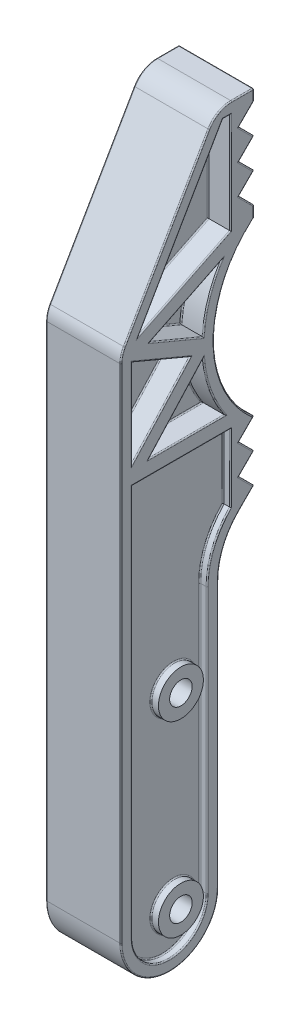
SolidWorks part; units mm, degrees
ref_plane "Front Plane" through (0, 0, 0) normal (0, 0, 1) x (1, 0, 0)
ref_plane "Top Plane" through (0, 0, 0) normal (0, 1, 0) x (1, 0, 0)
ref_plane "Right Plane" through (0, 0, 0) normal (1, 0, 0) x (0, 0, -1)
sketch "Sketch1" plane through (0, 0, 0) normal (1, 0, 0) x (0, 0, -1)
  line L0 (0, 0) -> (0, 90) construction
  line L1 (0, 90) -> (-5, 90) construction
  line L2 (-5, 90) -> (-17.75, 67.9164) construction
  line L3 (-17.75, 67.9164) -> (-17.75, 0) construction
  line L4 (-17.75, 0) -> (0, 0) construction
  line L5 (0, 88.5) -> (-2, 86.5)
  line L6 (0, 90) -> (-2, 90) construction
  line L7 (0, 90) -> (0, 75) construction
  line L8 (0, 75) -> (-2, 75) construction
  line L9 (-2, 90) -> (-2, 75) construction
  line L10 (-2, 86.5) -> (0, 84.5)
  line L11 (0, 84.5) -> (-2, 82.5)
  line L12 (-2, 82.5) -> (0, 80.5)
  line L13 (0, 80.5) -> (-2, 78.5)
  line L14 (-2, 78.5) -> (0, 76.5)
  line L15 (-17.75, 64.3) -> (0, 64.3) construction
  line L16 (-2, 42.1) -> (0, 44.1)
  line L17 (0, 44.1) -> (-2, 46.1)
  line L18 (-2, 46.1) -> (0, 48.1)
  line L19 (0, 48.1) -> (-2, 50.1)
  line L20 (-2, 50.1) -> (0, 52.1)
  line L21 (0, 76.5) -> (0, 75)
  line L22 (0, 88.5) -> (0, 90)
  line L23 (0, 90) -> (-5, 90)
  line L24 (-5, 90) -> (-17.75, 67.9164)
  line L25 (-17.75, 67.9164) -> (-17.75, 0)
  line L26 (-4.75, 0) -> (-4.75, 35.4609)
  line L27 (-9.75, 0) -> (-9.75, 25) construction
  arc A0 (0, 75) -> (0, 52.1) centre (9.6901, 63.55) ccw
  arc A1 (-17.75, 0) -> (-4.75, 0) centre (-11.25, 0) ccw
  arc A2 (-4.75, 35.4609) -> (-2, 42.1) centre (4.6391, 35.4609) cw
  circle A3 centre (-9.75, 0) radius 1.5
  circle A4 centre (-9.75, 25) radius 1.5
  dimension "D11" = 15
  dimension "D12" = 6.5
  dimension "D14" = 3
  dimension "D1" = 17.75
  dimension "D2" = 30
  dimension "D3" = 5
  dimension "D4" = 90
  dimension "D5" = 15
  dimension "D6" = 2
  dimension "D7" = 3.5
  dimension "D8" = 1.5
  dimension "D9" = 3
  dimension "D10" = 24.2
  dimension "D13" = 5
  dimension "D15" = 25
extrude "Boss-Extrude1" add sketch "Sketch1" along normal mid plane 10
sketch "Sketch2" plane through (0, 0, 0) normal (1, 0, 0) x (0, 0, -1)
  line L0 (-4.75, -8.4108) -> (-15, -8.4108)
  line L1 (-15, -8.4108) -> (-15, 23.5892)
  line L2 (-4.75, 35.4609) -> (-4.75, -8.4108)
  arc A0 (-15, 23.5892) -> (-4.75, 35.4609) centre (-3, 23.5892) cw
  dimension "D1" = 12
  dimension "D2" = 10.25
  dimension "D3" = 32
extrude "Cut-Extrude1" cut sketch "Sketch2" against normal mid plane 5
sketch "Sketch3" plane through (5, 0, 0) normal (1, 0, 0) x (0, 0, -1)
  line L17 (-3.1276, 88.5) -> (-3.1276, 43.0931)
  line L34 (-2.1213, 88.5) -> (-4.134, 88.5)
  line L35 (-4.134, 88.5) -> (-16.25, 67.5144)
  line L36 (-16.25, 67.5144) -> (-16.25, 0)
  line L37 (-6.25, 0) -> (-6.25, 35.4609)
  line L38 (-3.0607, 43.1607) -> (-2.1213, 44.1)
  line L39 (-2.1213, 44.1) -> (-4.1213, 46.1)
  line L40 (-4.1213, 46.1) -> (-2.1213, 48.1)
  line L41 (-2.1213, 48.1) -> (-4.1213, 50.1)
  line L42 (-4.1213, 50.1) -> (-2.1565, 52.0648)
  line L43 (-1.5, 75.6757) -> (-1.5, 75.8787)
  line L44 (-1.5, 75.8787) -> (-4.1213, 78.5)
  line L45 (-4.1213, 78.5) -> (-2.1213, 80.5)
  line L46 (-2.1213, 80.5) -> (-4.1213, 82.5)
  line L47 (-4.1213, 82.5) -> (-2.1213, 84.5)
  line L48 (-2.1213, 84.5) -> (-4.1213, 86.5)
  line L49 (-4.1213, 86.5) -> (-2.1213, 88.5)
  line L50 (-2.1213, 88.5) -> (-4.134, 88.5)
  line L51 (-4.134, 88.5) -> (-16.25, 67.5144)
  line L52 (-16.25, 67.5144) -> (-16.25, 0)
  line L53 (-6.25, 0) -> (-6.25, 35.4609)
  line L54 (-3.0607, 43.1607) -> (-2.1213, 44.1) construction
  line L55 (-2.1213, 44.1) -> (-4.1213, 46.1) construction
  line L56 (-4.1213, 46.1) -> (-2.1213, 48.1) construction
  line L57 (-2.1213, 48.1) -> (-4.1213, 50.1) construction
  line L58 (-4.1213, 50.1) -> (-2.1565, 52.0648) construction
  line L59 (-1.5, 75.6757) -> (-1.5, 75.8787) construction
  line L60 (-1.5, 75.8787) -> (-4.1213, 78.5) construction
  line L61 (-4.1213, 78.5) -> (-2.1213, 80.5) construction
  line L62 (-2.1213, 80.5) -> (-4.1213, 82.5) construction
  line L63 (-4.1213, 82.5) -> (-2.1213, 84.5) construction
  line L64 (-2.1213, 84.5) -> (-4.1213, 86.5) construction
  line L65 (-4.1213, 86.5) -> (-2.1213, 88.5) construction
  arc A6 (-16.25, 0) -> (-6.25, 0) centre (-11.25, 0) ccw
  arc A7 (-3.0607, 43.1607) -> (-6.25, 35.4609) centre (4.6391, 35.4609) ccw
  arc A8 (-1.5, 75.6757) -> (-2.1565, 52.0648) centre (9.6901, 63.55) ccw
  arc A9 (-16.25, 0) -> (-6.25, 0) centre (-11.25, 0) ccw
  arc A10 (-3.0607, 43.1607) -> (-6.25, 35.4609) centre (4.6391, 35.4609) ccw
  arc A11 (-1.5, 75.6757) -> (-2.1565, 52.0648) centre (9.6901, 63.55) ccw
  circle M20 centre (-9.75, 0) radius 1.5
  circle M41 centre (-9.75, 25) radius 1.5
  dimension "D1" = 1.5
extrude "Cut-Extrude2" cut sketch "Sketch3" against normal blind 1 contours A11 L17 L50 L51 L52 A9 L53 A10 M41 M20
sketch "Sketch4" plane through (4, 0, 0) normal (1, 0, 0) x (0, 0, -1)
  circle A0 centre (-9.75, 25) radius 1.5 construction
  circle A1 centre (-9.75, 25) radius 1.5
  circle A2 centre (-9.75, 0) radius 1.5 construction
  circle A3 centre (-9.75, 0) radius 1.5
extrude "Extrude-Thin1" add sketch "Sketch4" along normal blind 1 thin
sketch "Sketch5" plane through (4, 0, 0) normal (1, 0, 0) x (0, 0, -1)
  line L0 (-3.1276, 53.1598) -> (-16.25, 53.1598)
  line L6 (-3.1276, 73.9402) -> (-3.1276, 88.5)
  line L7 (-3.1276, 88.5) -> (-4.134, 88.5)
  line L8 (-4.134, 88.5) -> (-16.25, 67.5144)
  line L9 (-16.25, 67.5144) -> (-16.25, 0)
  line L10 (-6.25, 0) -> (-6.25, 35.4609)
  line L11 (-3.1276, 43.0931) -> (-3.1276, 53.1598)
  line L12 (-3.1276, 73.9402) -> (-3.1276, 88.5)
  line L13 (-3.1276, 88.5) -> (-4.134, 88.5)
  line L14 (-4.134, 88.5) -> (-16.25, 67.5144)
  line L15 (-16.25, 67.5144) -> (-16.25, 0)
  line L16 (-6.25, 0) -> (-6.25, 35.4609)
  line L17 (-3.1276, 43.0931) -> (-3.1276, 53.1598) construction
  arc A3 (-3.1276, 73.9402) -> (-3.1276, 53.1598) centre (9.6901, 63.55) ccw
  arc A4 (-16.25, 0) -> (-6.25, 0) centre (-11.25, 0) ccw
  arc A5 (-3.1276, 43.0931) -> (-6.25, 35.4609) centre (4.6391, 35.4609) ccw
  arc A6 (-3.1276, 73.9402) -> (-3.1276, 53.1598) centre (9.6901, 63.55) ccw
  arc A7 (-16.25, 0) -> (-6.25, 0) centre (-11.25, 0) ccw
  arc A8 (-3.1276, 43.0931) -> (-6.25, 35.4609) centre (4.6391, 35.4609) ccw construction
  arc M11 (-3.1276, 53.1598) -> (-3.1276, 73.9402) centre (9.6901, 63.55) cw
  line M12 (-3.1276, 73.9402) -> (-3.1276, 88.5)
  line M13 (-3.1276, 88.5) -> (-4.134, 88.5)
  line M14 (-4.134, 88.5) -> (-16.25, 67.5144)
  line M15 (-16.25, 67.5144) -> (-16.25, 0)
  dimension "D1" = 0
extrude "Cut-Extrude3" cut sketch "Sketch5" against normal blind 2 contours L0 M11 M12 M13 M14 M15
sketch "Sketch6" plane through (5, 0, 0) normal (1, 0, 0) x (0, 0, -1)
  line L0 (-3.1276, 53.1598) -> (-16.25, 53.1598)
  line L1 (-16.25, 53.1598) -> (-6.8099, 63.55)
  line L2 (-6.8099, 63.55) -> (-16.25, 67.5144)
  line L3 (-16.25, 67.5144) -> (-3.1276, 73.9402)
  arc A0 (-3.1276, 73.9402) -> (-3.1276, 53.1598) centre (9.6901, 63.55) ccw construction
extrude "Extrude-Thin2" add sketch "Sketch6" against normal up to body separate body thin thin type mid plane wall 2
sketch "Sketch7" plane through (2, 0, 0) normal (1, 0, 0) x (0, 0, -1)
  line L0 (-3.5674, 74.8383) -> (-3.1276, 73.9402)
  line L1 (-3.5674, 74.8383) -> (-3.1276, 73.9402) construction
  line L2 (-3.1276, 73.9402) -> (-3.5674, 74.8383) construction
  line L3 (-3.1276, 73.9402) -> (-3.1276, 75.0536)
  line L4 (-3.1276, 73.9402) -> (-3.1276, 88.5) construction
  line L5 (-3.1276, 75.0536) -> (-3.5674, 74.8383)
extrude "Boss-Extrude2" add sketch "Sketch7" along normal up to surface (3 mm away) up to face at (5, 68.1956, 8.4724)
mirror "Mirror1" about plane through (0, 0, 0) normal (1, 0, 0) of "Boss-Extrude2", "Extrude-Thin2", "Cut-Extrude3", "Extrude-Thin1", "Cut-Extrude2", "Cut-Extrude1"
fillet "Fillet1" radius 3.5 2 edges at (0, 90, 5) (0, 67.9164, 17.75)
fillet "Fillet2" radius 0.15 125 edges at (4, 25, 6.75) (4, 0, 6.75) (2, 78.7834, 9.7439) (2, 88.5, 3.6308) (2, 57.9576, 5.8333) (2, 68.576, 6.0258) (2, 60.5384, 16.25) (5, 60.5384, 16.25) (5, 26.0799, 16.25) (4, 26.0799, 16.25) (5, 47.6264, 3.1276) (4, 47.6264, 3.1276) (5, 68.576, 6.0258) (5, 57.9576, 5.8333) (5, -6.5, 11.25) (2, 69.9085, 9.0871) (2, 66.1021, 10.3044) (2, 58.145, 10.3695) (2, 54.1598, 8.9338) (4, 52.1598, 9.6888) (5, 52.1598, 9.6888) (2, 58.9113, 12.3756) (5, 58.9113, 12.3756) (2, 64.8027, 12.3756) (5, 64.8027, 12.3756) (5, 72.0602, 9.2407) (2, 72.0602, 9.2407) (5, 54.1598, 8.9338) (5, 58.145, 10.3695) (5, 66.1021, 10.3044) (5, 69.9085, 9.0871) (-5, 89.25, 0) (-5, 87.5, 1) (-5, 85.5, 1) (-5, 83.5, 1) (2, 81.7768, 3.1276) (5, 17.7305, 4.75) (-5, 81.5, 1) (-5, 79.5, 1) (-5, 77.5, 1) (-5, 75.75, 0) (-5, 63.55, 5.3099) (-5, 51.1, 1) (-5, 49.1, 1) (-5, 47.1, 1) (-5, 88.5, 3.6308) (-5, 78.7834, 9.7439) (-5, -5, 11.25) (-5, 17.7305, 6.25) (-4, 39.584, 5.4392) (-5, 45.1, 1) (-4, -5, 11.25) (-4, 17.7305, 6.25) (-5, 39.584, 5.4392) (-5, 81.7768, 3.1276) (-5, 43.1, 1) (5, 39.054, 4.0353) (-5, 39.054, 4.0353) (-5, 17.7305, 4.75) (-5, -6.5, 11.25) (-4, 25, 12.75) (-4, 0, 12.75) (-5, 90, 1.4896) (-2, 88.5, 3.6308) (-2, 78.7834, 9.7439) (5, 43.1, 1) (-2, 60.5384, 16.25) (-2, 57.9576, 5.8333) (-2, 68.576, 6.0258) (-4, 47.6264, 3.1276) (-4, 26.0799, 16.25) (-5, 47.6264, 3.1276) (-5, 60.5384, 16.25) (-5, 26.0799, 16.25) (-5, 68.576, 6.0258) (-5, 57.9576, 5.8333) (-2, 72.0602, 9.2407) (-2, 64.8027, 12.3756) (-2, 58.9113, 12.3756) (-4, 52.1598, 9.6888) (-2, 54.1598, 8.9338) (-5, 54.1598, 8.9338) (-2, 58.145, 10.3695) (-5, 58.145, 10.3695) (-2, 66.1021, 10.3044) (-5, 66.1021, 10.3044) (-2, 69.9085, 9.0871) (-5, 69.9085, 9.0871) (-5, 52.1598, 9.6888) (-5, 58.9113, 12.3756) (-5, 64.8027, 12.3756) (-5, 72.0602, 9.2407) (5, 45.1, 1) (0, 90, 0) (-2, 81.7768, 3.1276) (-5, 78.4893, 11.6457) (5, 78.4893, 11.6457) (-5, 33.4893, 17.75) (-5, 67.8844, 17.6307) (-5, 89.5311, 4.7293) (5, 33.4893, 17.75) (5, 67.8844, 17.6307) (5, 89.5311, 4.7293) (5, 47.1, 1) (5, 49.1, 1) (5, 51.1, 1) (5, 63.55, 5.3099) (5, 90, 1.4896) (5, 75.75, 0) (5, 77.5, 1) (5, 79.5, 1) (5, 81.5, 1) (5, 83.5, 1) (5, 85.5, 1) (5, 87.5, 1) (5, 89.25, 0) (5, 39.584, 5.4392) (4, 17.7305, 6.25) (4, -5, 11.25) (5, 81.7768, 3.1276) (4, 39.584, 5.4392) (5, 88.5, 3.6308) (5, 78.7834, 9.7439) (5, -5, 11.25) (5, 17.7305, 6.25)
